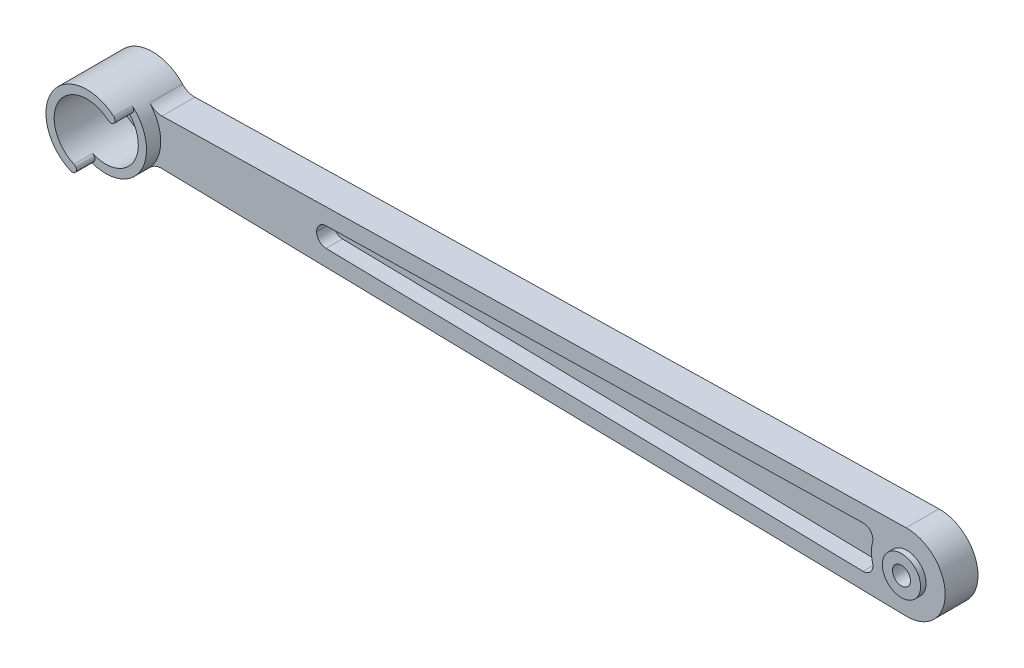
SolidWorks part; units mm, degrees
material "6061-T6 (SS)"
ref_plane "Front Plane" through (0, 0, 0) normal (0, 0, 1) x (1, 0, 0)
ref_plane "Top Plane" through (0, 0, 0) normal (0, 1, 0) x (1, 0, 0)
ref_plane "Right Plane" through (0, 0, 0) normal (1, 0, 0) x (0, 0, -1)
sketch "Sketch1" plane through (0, 0, 0) normal (0, 0, 1) x (1, 0, 0)
  line L0 (-0.1458, 6.9985) -> (-144.0833, 3.9991)
  line L1 (-0.1458, -6.9985) -> (-144.0833, -3.9991)
  circle A0 centre (-144, 0) radius 7.5
  circle A1 centre (0, 0) radius 7
  circle A2 centre (-144, 0) radius 4
  circle A3 centre (-144, 0) radius 6
  point P6 (-140, 0)
  dimension "D1" = 12
  dimension "D2" = 14
  dimension "D4" = 8
  dimension "D5" = 15
  dimension "D3" = 140
extrude "Boss-Extrude1" add sketch "Sketch1" along normal blind 6 contours A2 L1 A1 L0 | A1 | A3 L1 A0 L0 | A3 L0 A0 L1 region at (-65.7802, 0, 0) region at (0, 0, 0) region at (-137.7298, 0, 0) region at (-138.6805, 4.3153, 0)
sketch "Sketch2" plane through (0, 0, 6) normal (0, 0, 1) x (1, 0, 0)
  circle A1 centre (0, 0) radius 3.5
  dimension "D1" = 7
extrude "Boss-Extrude2" add sketch "Sketch2" along normal blind 1
sketch "Sketch4" plane through (0, 0, 7) normal (0, 0, 1) x (1, 0, 0)
  circle A0 centre (0, 0) radius 1.65
  dimension "D1" = 3.3
extrude "Cut-Extrude1" cut sketch "Sketch4" against normal blind 12
sketch "Sketch6" plane through (0, 0, 0) normal (0, 0, -1) x (-1, 0, 0)
  circle A0 centre (144, 0) radius 5
  circle A1 centre (144, 0) radius 6
  circle A2 centre (144, 0) radius 6 construction
  dimension "D1" = 1
extrude "Boss-Extrude4" add sketch "Sketch6" against normal blind 0.6
fillet "Fillet3" radius 3 2 edges at (-137.7404, -4.1313, 3) (-137.7404, 4.1313, 3)
sketch "Sketch7" plane through (0, 0, 6) normal (0, 0, 1) x (1, 0, 0)
  line L0 (-144, 0) -> (-138.5152, 5.1154)
  line L1 (-144, 0) -> (-146.1923, -7.1724)
  arc A0 (-138.5152, 5.1154) -> (-138.5152, -5.1154) centre (-144, 0) ccw construction
  arc A1 (-146.1923, -7.1724) -> (-138.5152, 5.1154) centre (-144, 0) cw
  arc A2 (-145.7538, -5.738) -> (-139.6122, 4.0923) centre (-144, 0) cw
  arc M6 (-138.5152, 5.1154) -> (-138.5152, -5.1154) centre (-144, 0) ccw
  dimension "D1" = 1.5
  dimension "D2" = 150
extrude "Boss-Extrude5" add sketch "Sketch7" along normal blind 6 contours L1 A2 L0 M6 region at (-149.2547, 3.283, 6)
fillet "Fillet1" radius 0.75 4 edges at (-146.1923, -7.1724, 9) (-145.7538, -5.738, 9) (-139.6122, 4.0923, 9) (-138.5152, 5.1154, 9)
sketch "Sketch8" plane through (0, 0, 6) normal (0, 0, 1) x (1, 0, 0)
  line L0 (-8.0189, 3.8338) -> (-106.2622, 1.7866)
  line L1 (-8.0189, -3.8338) -> (-106.2622, -1.7866)
  line L2 (-0.1458, -6.9985) -> (-136.2588, -4.1622) construction
  line L7 (-0.1458, 6.9985) -> (-136.2588, 4.1622) construction
  arc A0 (-6.2892, 1.6421) -> (-6.2892, -1.6421) centre (0, 0) ccw
  arc A1 (-107.9757, 0.0353) -> (-107.9757, -0.0353) centre (-144, 0) cw
  circle A2 centre (0, 0) radius 3.5 construction
  arc A3 (-106.2622, -1.7866) -> (-107.9757, -0.0353) centre (-106.2257, -0.037) cw
  arc A4 (-106.2622, 1.7866) -> (-107.9757, 0.0353) centre (-106.2257, 0.037) ccw
  arc A5 (-8.0189, -3.8338) -> (-6.2892, -1.6421) centre (-7.9824, -2.0842) ccw
  arc A6 (-6.2892, 1.6421) -> (-8.0189, 3.8338) centre (-7.9824, 2.0842) ccw
  point P16 (-108.0182, -1.75)
  point P19 (-108.0182, 1.75)
  dimension "D3" = 3
  dimension "D5" = 1.75
  dimension "D1" = 3
  dimension "D2" = 3
  dimension "D4" = 3.5
extrude "Cut-Extrude2" cut sketch "Sketch8" against normal blind 3
sketch "Sketch9" plane through (0, 0, 6) normal (0, 0, 1) x (1, 0, 0)
  circle A0 centre (-144, 0) radius 6
  circle A1 centre (-144, 0) radius 7.5
  circle A2 centre (-144, 0) radius 6 construction
  arc A3 (-146.9756, -6.8844) -> (-138.5152, -5.1154) centre (-144, 0) ccw construction
extrude "Boss-Extrude6" add sketch "Sketch9" along normal blind 2.6
